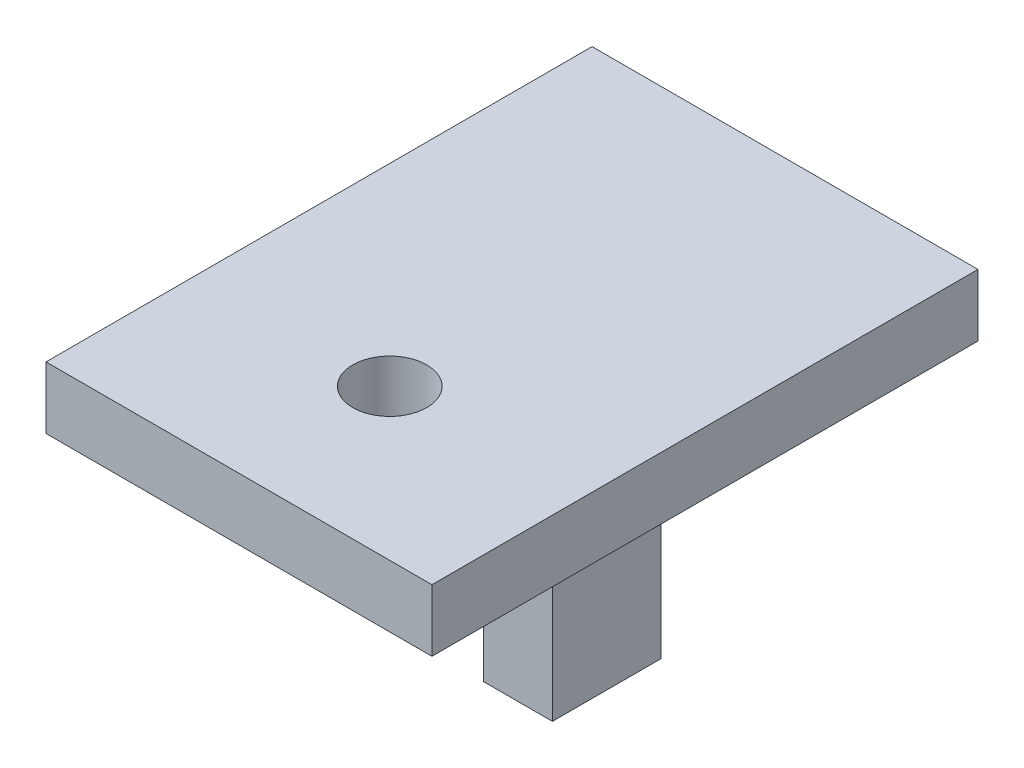
SolidWorks part; units mm, degrees
ref_plane "Front Plane" through (0, 0, 0) normal (0, 0, 1) x (1, 0, 0)
ref_plane "Top Plane" through (0, 0, 0) normal (0, 1, 0) x (1, 0, 0)
ref_plane "Right Plane" through (0, 0, 0) normal (1, 0, 0) x (0, 0, -1)
sketch "Sketch1" plane through (0, 0, 0) normal (0, 1, 0) x (1, 0, 0)
  line L1 (-31.1, 40.4921) -> (31.1, 40.4921)
  line L2 (-31.1, 40.4921) -> (-31.1, -47.5179)
  line L3 (-31.1, -47.5179) -> (31.1, -47.5179)
  line L4 (31.1, 40.4921) -> (31.1, -47.5179)
  point P0 (0, 0)
  dimension "D1" = 62.2
  dimension "D2" = 88.01
extrude "Boss-Extrude1" add sketch "Sketch1" along normal blind 10
sketch "Sketch2" plane through (0, 10, 0) normal (0, 1, 0) x (1, 0, 0)
  line L0 (-31.1, -47.5179) -> (31.1, -47.5179) construction
  circle A0 centre (0, -23.2179) radius 5.969
  dimension "D1" = 24.3
extrude "Cut-Extrude1" cut sketch "Sketch2" against normal blind 10
sketch "Sketch3" plane through (0, 0, 0) normal (0, -1, 0) x (1, 0, 0)
  line L0 (31.1, -40.4921) -> (-31.1, -40.4921) construction
  line L1 (-20.01, -40.4921) -> (-31.1, -40.4921)
  line L2 (-20.01, -40.4921) -> (-20.01, -23.0094)
  line L3 (-20.01, -23.0094) -> (-31.1, -23.0094)
  line L4 (-31.1, -40.4921) -> (-31.1, -23.0094)
  line L5 (-31.1, -40.4921) -> (-31.1, 47.5179) construction
  dimension "D1" = 11.09
  dimension "D2" = 0
  dimension "D3" = 17.4826
  dimension "D4" = 0
extrude "Boss-Extrude2" add sketch "Sketch3" along normal blind 69.9
sketch "Sketch5" plane through (0, 0, 0) normal (0, -1, 0) x (-1, 0, 0)
  circle A0 centre (0, -23.2179) radius 50
sketch "Sketch14" plane through (0, 0, 0) normal (0, -1, 0) x (1, 0, 0)
  line L0 (-25.9089, -38.0083) -> (-20.0089, -38.0092) construction
  line L1 (-20.0089, -38.0092) -> (-20.007, -25.1092) construction
  line L2 (-25.9089, -38.0083) -> (-20.0089, -38.0092)
  line L3 (-20.0089, -38.0092) -> (-20.007, -25.1092)
